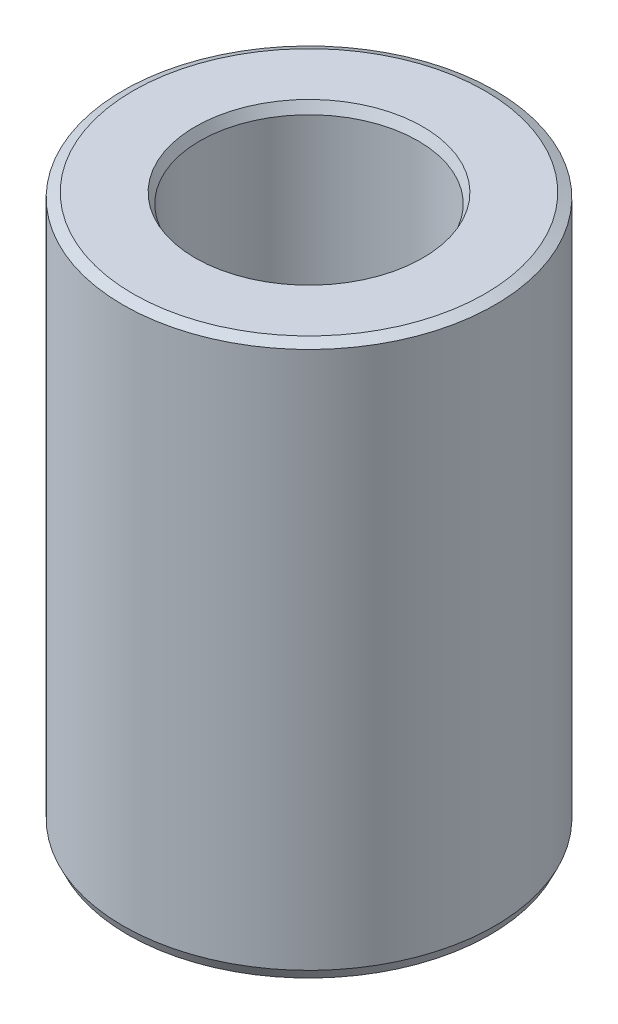
SolidWorks part; units mm, degrees
ref_plane "Front Plane" through (0, 0, 0) normal (0, 0, 1) x (1, 0, 0)
ref_plane "Top Plane" through (0, 0, 0) normal (0, 1, 0) x (1, 0, 0)
ref_plane "Right Plane" through (0, 0, 0) normal (1, 0, 0) x (0, 0, -1)
sketch "Sketch1" plane through (0, 0, 0) normal (0, 1, 0) x (1, 0, 0)
  circle A0 centre (0, 0) radius 47.5
  dimension "SLEEVE_OD" = 95
extrude "Boss-Extrude1" add sketch "Sketch1" along normal blind 141.1631
sketch "Sketch2" plane through (0, 0, 0) normal (0, 1, 0) x (1, 0, 0)
  circle A0 centre (0, 0) radius 27.8811
  dimension "BORE_D" = 55.7622
extrude "Cut-Extrude1" cut sketch "Sketch2" along normal through all
chamfer "Chamfer1" distance 1.1985 angle 64.772 4 edges at (0, 141.1631, 27.8811) (0, 0, 27.8811) (0, 0, 47.5) (0, 141.1631, 47.5) first distance on face at (0, 141.1631, 27.8811) first distance on face at (0, 0, 27.8811) first distance on face at (0, 141.1631, 47.5)
